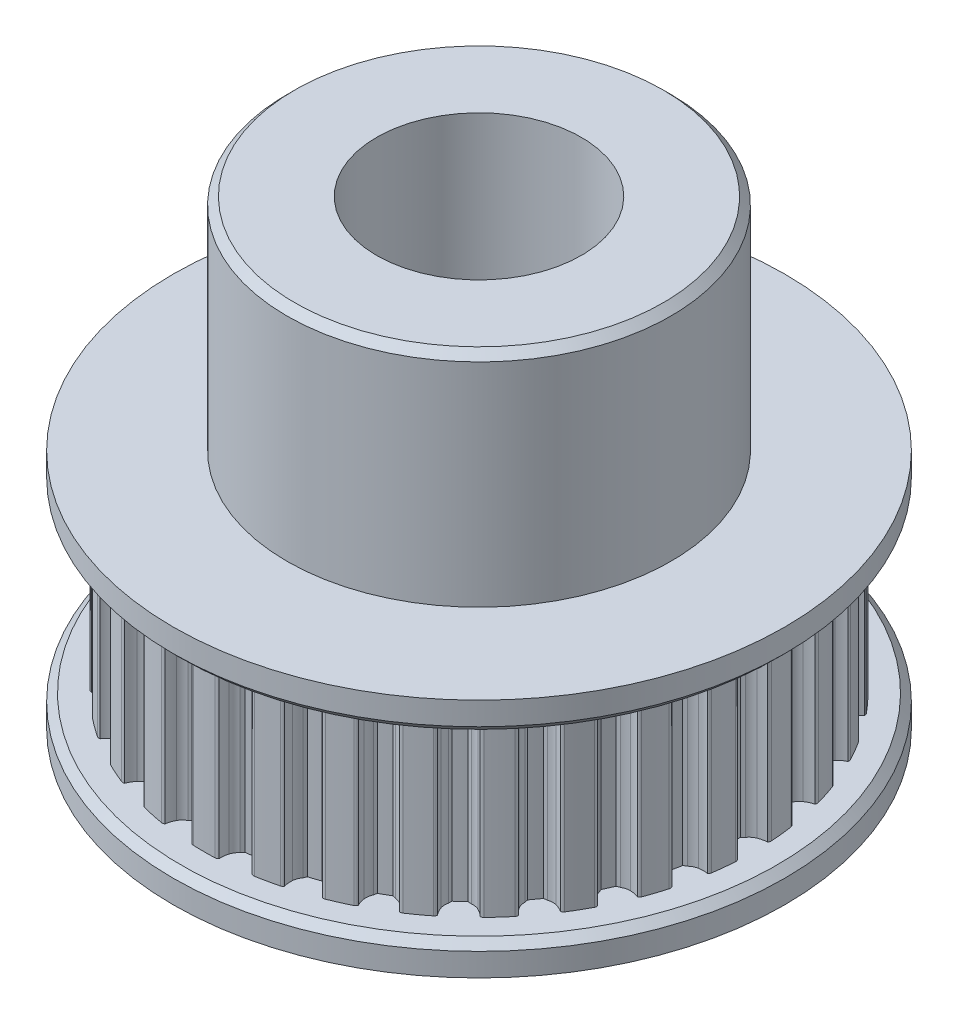
SolidWorks part; units mm, degrees
ref_plane "Front Plane" through (0, 0, 0) normal (0, 0, 1) x (1, 0, 0)
ref_plane "Top Plane" through (0, 0, 0) normal (0, 1, 0) x (1, 0, 0)
ref_plane "Right Plane" through (0, 0, 0) normal (1, 0, 0) x (0, 0, -1)
sketch "Sketch1" plane through (0, 0, 0) normal (0, 1, 0) x (1, 0, 0)
  line L0 (0, 0) -> (0, 11) construction
  line L1 (0, 0) -> (1.1498, 10.9397) construction
  line L2 (0, 0) -> (1.6069, 10.882) construction
  circle A0 centre (0, 0) radius 11 construction
  circle A1 centre (0, 0) radius 9.996 construction
  circle A2 centre (0, 0) radius 10.746 construction
  arc A3 (1.0449, 9.9412) -> (0.5705, 10.3364) centre (1.1029, 10.4932) cw
  arc A4 (2.5291, 10.9132) -> (0.5705, 10.5933) centre (1.5698, 10.6307) cw
  circle A5 centre (0, 0) radius 10.596 construction
  arc A6 (-0.4266, 10.7375) -> (0.4266, 10.7375) centre (0, 0) cw
  arc A7 (0.4266, 10.7375) -> (0.5705, 10.5933) centre (0.4206, 10.5876) cw
  arc A8 (2.5291, 10.9132) -> (0.5705, 10.3364) centre (1.5498, 10.6248) ccw
  arc A9 (-1.0449, 9.9412) -> (-0.5705, 10.3364) centre (-1.1029, 10.4932) ccw
  arc A10 (-2.5291, 10.9132) -> (-0.5705, 10.3364) centre (-1.5498, 10.6248) cw
  arc A11 (-2.5291, 10.9132) -> (-0.5705, 10.5933) centre (-1.5698, 10.6307) ccw
  arc A12 (-0.4266, 10.7375) -> (-0.5705, 10.5933) centre (-0.4206, 10.5876) ccw
  arc A13 (-1.0449, 9.9412) -> (1.0449, 9.9412) centre (0, 0) cw
  point P13 (1.5698, 10.6307)
  point P16 (0, 10.746)
  dimension "D1" = 22
  dimension "D6" = 0.555
  dimension "D7" = 1
  dimension "D9" = 0.15
  dimension "D2" = 6
  dimension "D3" = 2.4
  dimension "D4" = 1.004
  dimension "D5" = 0.75
  dimension "D8" = 0.15
extrude "Boss-Extrude1" add sketch "Sketch1" along normal blind 7 contours A9 A13 A3 A8 A4 A7 A6 A12 A11 A10
sketch "Sketch2" plane through (0, 0, 0) normal (0, -1, 0) x (1, 0, 0)
  circle A0 centre (0, 0) radius 9.996
  arc A2 (-0.8265, -9.9618) -> (0.8265, -9.9618) centre (0, 0) ccw construction
  arc A5 (-0.8265, -9.9618) -> (0.8265, -9.9618) centre (0, 0) ccw
  arc M3 (-0.739, -10.0741) -> (-0.5705, -10.3364) centre (-1.1029, -10.4932) cw
  arc M4 (-0.5705, -10.3364) -> (-0.5309, -10.6893) centre (-1.5498, -10.6248) cw
  arc M5 (-0.8265, -9.9618) -> (-0.739, -10.0741) centre (-1.5698, -10.6307) cw
  arc M6 (-0.5309, -10.6893) -> (-0.4266, -10.7375) centre (-0.4206, -10.5876) ccw
  arc M7 (-0.4266, -10.7375) -> (0.4266, -10.7375) centre (0, 0) ccw
  arc M8 (0.4266, -10.7375) -> (0.5309, -10.6893) centre (0.4206, -10.5876) ccw
  arc M9 (0.739, -10.0741) -> (0.8265, -9.9618) centre (1.5698, -10.6307) cw
  arc M10 (0.5309, -10.6893) -> (0.5705, -10.3364) centre (1.5498, -10.6248) cw
  arc M11 (0.5705, -10.3364) -> (0.739, -10.0741) centre (1.1029, -10.4932) cw
  arc M12 (0.8265, -9.9618) -> (-0.8265, -9.9618) centre (0, 0) cw
extrude "Boss-Extrude2" add sketch "Sketch2" against normal blind 7 contours A0 M3 M12 M11 M10 M9 M8 M7 M6 M5 M4
pattern_circular "CirPattern3" count 30 over 360 about axis through (0, 0, 0) along (0, 1, 0) of "Boss-Extrude1"
sketch "Sketch3" plane through (0, 7, 0) normal (0, 1, 0) x (1, 0, 0)
  circle A0 centre (0, 0) radius 11.946
  arc A3 (0.4742, 11.9366) -> (-0.4742, 11.9366) centre (0, 0) ccw
  arc A4 (0.4742, 11.9366) -> (-0.4742, 11.9366) centre (0, 0) ccw
  dimension "D1" = 1.2
extrude "Boss-Extrude3" add sketch "Sketch3" along normal blind 1.2 contours A0
sketch "Sketch4" plane through (0, 0, 0) normal (0, -1, 0) x (1, 0, 0)
  circle A0 centre (0, 0) radius 11.946 construction
  circle A1 centre (0, 0) radius 11.946
extrude "Boss-Extrude4" add sketch "Sketch4" along normal blind 1.2
sketch "Sketch12" plane through (0, 8.2, 0) normal (0, 1, 0) x (1, 0, 0)
  circle A0 centre (0, 0) radius 7.5
  dimension "D1" = 15
extrude "Boss-Extrude10" add sketch "Sketch12" along normal offset from surface (8.6 mm away) 18 up to face at (0, -1.2, -11.946)
sketch "Sketch5" plane through (0, 8.2, 0) normal (0, 1, 0) x (1, 0, 0)
  circle A0 centre (0, 0) radius 4
  dimension "D1" = 8
extrude "Cut-Extrude1" cut sketch "Sketch5" against normal through all both and the other way through all
chamfer "Chamfer1" distance 0.3 angle 45 3 edges at (0, 7, 11.946) (0, 0, -11.946) (0, 16.8, -7.5)
equation "\"TeethNumber\"=30"
equation "\"Pitch\"= 2"
equation "\"PulleyDiameter\"= \"TeethNumber\" * \"Pitch\" / PI"
equation "\"ToothAngle\"= ( 360 / \"TeethNumber\" )"
equation "\"TransOffsetAngle\"= \"ToothAngle\" * 0.2' "
equation "\"ShoulderRadius\"= 0.15"
equation "\"RootRadius\"= 0.555"
equation "\"TransRadius\"= 1"
equation "\"ToothHeight\"= 0.75"
equation "\"PLD\"= 0.254"
equation "\"D2@Sketch1\"=\"ToothAngle\"/2"
equation "\"D3@Sketch1\"=\"TransOffsetAngle\""
equation "\"D4@Sketch1\"=\"PLD\"+\"ToothHeight\""
equation "\"D5@Sketch1\"=\"ToothHeight\""
equation "\"D6@Sketch1\" = \"RootRadius\""
equation "\"D7@Sketch1\"=\"TransRadius\""
equation "\"D9@Sketch1\"=\"ShoulderRadius\""
equation "\"TeethNumber-2\"= 23"
equation "\"PulleyDiameter-2\"= \"TeethNumber-2\" * \"Pitch\" / PI"
equation "\"ToothAngle-2\"= 360/\"TeethNumber-2\""
equation "\"TransOffsetAngle-2\"= \"ToothAngle-2\" * 0.2"
equation "\"D1@Sketch6\"=\"PulleyDiameter-2\""
equation "\"D2@Sketch6\"=\"ToothAngle-2\"/2"
equation "\"D3@Sketch6\"=\"TransOffsetAngle-2\""
equation "\"D4@Sketch6\"=\"PLD\"+\"ToothHeight\""
equation "\"D5@Sketch6\"=\"ToothHeight\""
equation "\"D6@Sketch6\"=\"ShoulderRadius\""
equation "\"D7@Sketch6\"=\"RootRadius\""
equation "\"D8@Sketch6\"=\"TransRadius\""
equation "\"D9@Sketch6\"=\"ShoulderRadius\""
equation "\"D1@CirPattern3\"=\"TeethNumber\""
equation "\"D1@CirPattern4\"=\"TeethNumber-2\""
